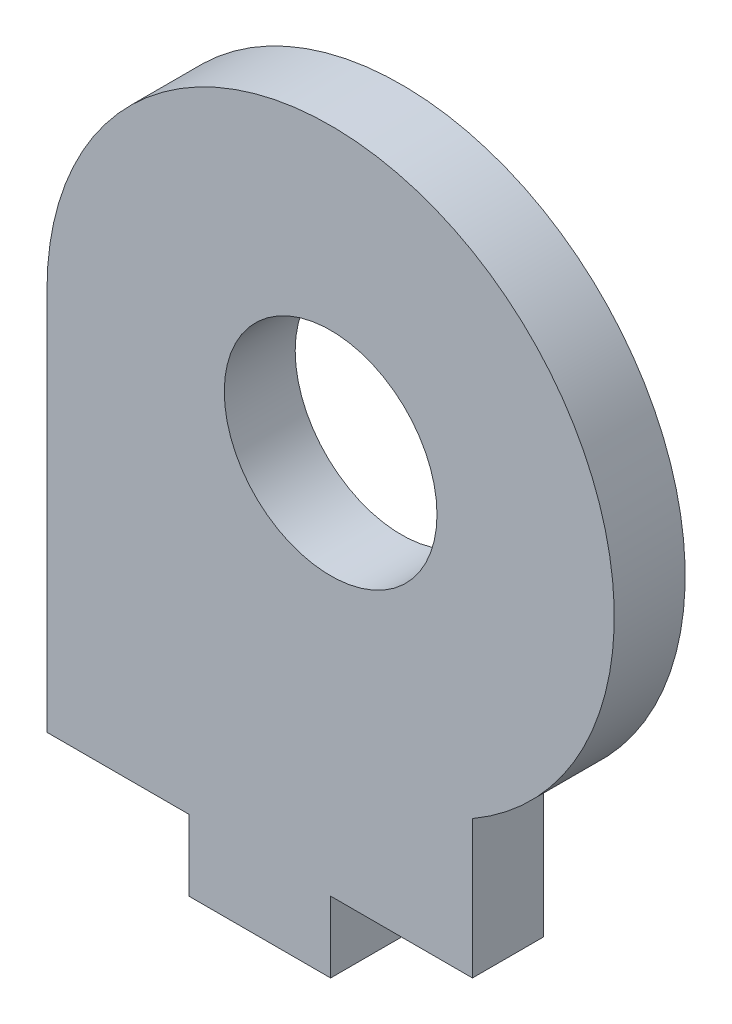
SolidWorks part; units mm, degrees
ref_plane "Front Plane" through (0, 0, 0) normal (0, 0, 1) x (1, 0, 0)
ref_plane "Top Plane" through (0, 0, 0) normal (0, 1, 0) x (1, 0, 0)
ref_plane "Right Plane" through (0, 0, 0) normal (1, 0, 0) x (0, 0, -1)
sketch "Sketch1" plane through (0, 0, 0) normal (0, 0, 1) x (1, 0, 0)
  line L0 (7.9877, 0) -> (20.6877, 0) construction
  line L1 (20.6877, 0) -> (20.6877, 20.3568) construction
  line L2 (20.6877, 20.3568) -> (20.6877, 33.0568) construction
  line L3 (20.6877, 20.3568) -> (15.9252, 20.3568) construction
  line L5 (7.9877, 20.3568) -> (7.9877, 0)
  line L12 (33.2915, 21.9172) -> (33.2915, 0) construction
  line L13 (7.9877, 0) -> (27.0377, 0)
  line L14 (27.0377, 0) -> (27.0377, 9.3583)
  circle A0 centre (20.6877, 20.3568) radius 4.7625
  arc A10 (27.0377, 9.3583) -> (7.9877, 20.3568) centre (20.6877, 20.3568) ccw
  arc A11 (27.0377, 9.3583) -> (20.6877, 7.6568) centre (20.6877, 20.3568) ccw construction
  dimension "D2" = 9.525
  dimension "D4" = 19.05
  dimension "D1" = 20.3568
extrude "Boss-Extrude1" add sketch "Sketch1" along normal blind 3.175
sketch "Sketch2" plane through (0, 0, 0) normal (0, -1, 0) x (1, 0, 0)
  line L0 (7.9877, 3.175) -> (27.0377, 3.175) construction
  line L1 (7.9877, 0) -> (14.3377, 0)
  line L2 (7.9877, 0) -> (7.9877, 3.175)
  line L3 (7.9877, 3.175) -> (14.3377, 3.175)
  line L4 (14.3377, 0) -> (14.3377, 3.175)
  line L6 (27.0377, 0) -> (20.6877, 0)
  line L7 (27.0377, 0) -> (27.0377, 3.175)
  line L8 (27.0377, 3.175) -> (20.6877, 3.175)
  line L9 (20.6877, 0) -> (20.6877, 3.175)
  dimension "D1" = 6.35
  dimension "D2" = 6.35
extrude "Cut-Extrude1" cut sketch "Sketch2" against normal blind 3.175
